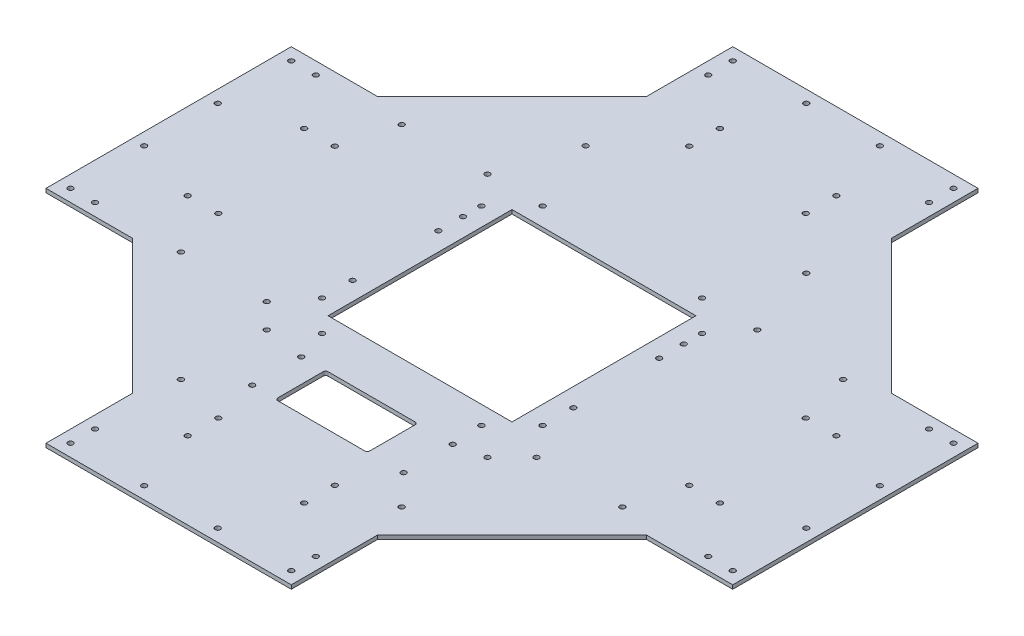
SolidWorks part; units mm, degrees
ref_plane "Front Plane" through (0, 0, 0) normal (0, 0, 1) x (1, 0, 0)
ref_plane "Top Plane" through (0, 0, 0) normal (0, 1, 0) x (1, 0, 0)
ref_plane "Right Plane" through (0, 0, 0) normal (1, 0, 0) x (0, 0, -1)
sketch "Sketch1" plane through (0, 0, 0) normal (0, 1, 0) x (1, 0, 0)
  line L0 (0, -280) -> (100, -280)
  line L1 (100, -280) -> (100, -209.6016)
  line L2 (280, -100) -> (209.6016, -100)
  line L3 (0, 0) -> (0, -280) construction
  line L4 (280, 0) -> (280, -100)
  line L5 (-280, 280) -> (280, 280) construction
  line L6 (-280, 280) -> (-280, -280) construction
  line L7 (-280, -280) -> (280, -280) construction
  line L8 (280, 280) -> (280, -280) construction
  line L9 (-280, 280) -> (280, -280) construction
  line L10 (-280, -280) -> (280, 280) construction
  line L11 (100, -209.6016) -> (209.6016, -100)
  line L12 (-280, 0) -> (-280, -100)
  line L13 (-280, -100) -> (-209.6016, -100)
  line L14 (-209.6016, -100) -> (-100, -209.6016)
  line L15 (-100, -280) -> (-100, -209.6016)
  line L16 (0, -280) -> (-100, -280)
  line L17 (0, 280) -> (-100, 280)
  line L18 (-100, 280) -> (-100, 209.6016)
  line L19 (-100, 209.6016) -> (-209.6016, 100)
  line L20 (-280, 100) -> (-209.6016, 100)
  line L21 (-280, 0) -> (-280, 100)
  line L22 (280, 0) -> (280, 100)
  line L23 (280, 100) -> (209.6016, 100)
  line L24 (209.6016, 100) -> (100, 209.6016)
  line L25 (100, 280) -> (100, 209.6016)
  line L26 (0, 280) -> (100, 280)
  line L27 (111.5258, -219.2889) -> (219.2889, -111.5258) construction
  line L28 (219.2889, -111.5258) -> (247.5732, -139.8101) construction
  line L29 (247.5732, -139.8101) -> (139.8101, -247.5732) construction
  line L30 (139.8101, -247.5732) -> (111.5258, -219.2889) construction
  line L31 (-100, -270) -> (100, -270) construction
  line L32 (-90, -280) -> (-90, 280) construction
  line L37 (-70, -70) -> (70, 70) construction
  line L38 (-70, 70) -> (70, -70) construction
  line L39 (-100, -260) -> (100, -260) construction
  line L40 (-280, 40) -> (280, 40) construction
  line L41 (0, 280) -> (0, 0) construction
  line L42 (-280, -90) -> (280, -90) construction
  line L43 (-260, -100) -> (-260, 100) construction
  line L44 (0, 0) -> (-280, 0) construction
  arc A0 (100, -280) -> (280, -100) centre (100, -100) ccw construction
  circle A1 centre (-47.5, -192) radius 2.125
  circle A2 centre (-47.5, -217) radius 2.125
  circle A3 centre (47.5, -217) radius 2.125
  circle A4 centre (47.5, -192) radius 2.125
  circle A5 centre (-192, 47.5) radius 2.125
  circle A6 centre (-217, 47.5) radius 2.125
  circle A7 centre (-192, -47.5) radius 2.125
  circle A8 centre (-217, -47.5) radius 2.125
  circle A9 centre (47.5, 192) radius 2.125
  circle A10 centre (47.5, 217) radius 2.125
  circle A11 centre (-47.5, 192) radius 2.125
  circle A12 centre (-47.5, 217) radius 2.125
  circle A13 centre (192, -47.5) radius 2.125
  circle A14 centre (217, -47.5) radius 2.125
  circle A15 centre (192, 47.5) radius 2.125
  circle A16 centre (217, 47.5) radius 2.125
  circle A17 centre (-90, -270) radius 2.125
  circle A18 centre (-30, -270) radius 2.125
  circle A19 centre (30, -270) radius 2.125
  circle A20 centre (90, -270) radius 2.125
  circle A21 centre (-270, 90) radius 2.125
  circle A22 centre (-270, 30) radius 2.125
  circle A23 centre (-270, -30) radius 2.125
  circle A24 centre (-270, -90) radius 2.125
  circle A25 centre (90, 270) radius 2.125
  circle A26 centre (30, 270) radius 2.125
  circle A27 centre (-30, 270) radius 2.125
  circle A28 centre (-90, 270) radius 2.125
  circle A29 centre (270, -90) radius 2.125
  circle A30 centre (270, -30) radius 2.125
  circle A31 centre (270, 30) radius 2.125
  circle A32 centre (270, 90) radius 2.125
  circle A33 centre (-90, -250) radius 2.125
  circle A34 centre (-90, -180) radius 2.125
  circle A35 centre (-90, -110) radius 2.125
  circle A36 centre (-90, -40) radius 2.125
  circle A37 centre (-90, 30) radius 2.125
  circle A38 centre (-90, 50) radius 2.125
  circle A39 centre (-90, 100) radius 2.125 construction
  circle A40 centre (-90, 150) radius 2.125
  circle A41 centre (-90, 200) radius 2.125 construction
  circle A42 centre (-90, 250) radius 2.125
  circle A43 centre (90, -250) radius 2.125
  circle A44 centre (90, -180) radius 2.125
  circle A45 centre (90, -110) radius 2.125
  circle A46 centre (90, -40) radius 2.125
  circle A47 centre (90, 30) radius 2.125
  circle A48 centre (90, 50) radius 2.125
  circle A49 centre (90, 100) radius 2.125 construction
  circle A50 centre (90, 150) radius 2.125
  circle A51 centre (90, 200) radius 2.125 construction
  circle A52 centre (90, 250) radius 2.125
  circle A53 centre (-250, -90) radius 2.125
  circle A54 centre (-180, -90) radius 2.125
  circle A55 centre (-110, -90) radius 2.125
  circle A56 centre (-110, 90) radius 2.125
  circle A57 centre (-180, 90) radius 2.125
  circle A58 centre (-250, 90) radius 2.125
  circle A59 centre (110, -90) radius 2.125
  circle A60 centre (180, -90) radius 2.125
  circle A61 centre (250, -90) radius 2.125
  circle A62 centre (110, 90) radius 2.125
  circle A63 centre (180, 90) radius 2.125
  circle A64 centre (250, 90) radius 2.125
  point P33 (0, 0)
  point P68 (0, 0)
  point P107 (0, 0)
  dimension "D10" = 25
  dimension "4.25" = 4.25
  dimension "D11" = 4.25
  dimension "D16" = 4.25
  dimension "D24" = 4.25
  dimension "D28" = 4.25
  dimension "D32" = 4.25
  dimension "D1" = 560
  dimension "D2" = 90
  dimension "D3" = 280
  dimension "D4" = 4
  dimension "D5" = 100
  dimension "D6" = 155
  dimension "D7" = 152.4
  dimension "D8" = 15
  dimension "D9" = 40
  dimension "D12" = 47.5
  dimension "D13" = 63
  dimension "D15" = 10
  dimension "D17" = 10
  dimension "D18" = 76.2
  dimension "D23" = 10
  dimension "D25" = 10
  dimension "D26" = 300
  dimension "D29" = 10
  dimension "D31" = 20
  dimension "D33" = 10
  dimension "D21" = 4
  dimension "D27" = 5
  dimension "D30" = 5
  dimension "D34" = 3
  dimension "D14" = 4
  dimension "D22" = 4
extrude "Boss-Extrude1" add sketch "Sketch1" along normal blind 3.175 contours L26 L17 L18 L19 L20 L21 L12 L13 L14 L15 L16 L0 L1 L11 L2 L4 L22 L23 L24 L25 region at (0, 0, -0.0137)
sketch "Sketch2" plane through (0, 3.175, 0) normal (0, 1, 0) x (1, 0, 0)
  line L0 (-90, -280) -> (-90, 280) construction
  line L1 (-75, -75) -> (75, -75)
  line L2 (-75, -75) -> (-75, 75)
  line L3 (-75, 75) -> (75, 75)
  line L4 (75, -75) -> (75, 75)
  line L5 (-75, -75) -> (75, 75) construction
  line L6 (-75, 75) -> (75, -75) construction
  line L7 (-90, -280) -> (-90, 280) construction
  line L8 (-75, 0) -> (75, 0) construction
  line L9 (0, 75) -> (0, -75) construction
  line L10 (-110, 90) -> (110, 90) construction
  line L11 (37.5, -135) -> (-37.5, -135) construction
  line L16 (-37.5, -155.5) -> (37.5, -155.5)
  line L17 (-37.5, -155.5) -> (-37.5, -114.5)
  line L18 (-37.5, -114.5) -> (37.5, -114.5)
  line L19 (37.5, -155.5) -> (37.5, -114.5)
  line L20 (-37.5, -155.5) -> (37.5, -114.5) construction
  line L21 (-37.5, -114.5) -> (37.5, -155.5) construction
  circle A0 centre (66.6, -115) radius 2.125
  circle A1 centre (-90, 65) radius 2.125
  circle A2 centre (-90, -65) radius 2.125
  circle A3 centre (90, -65) radius 2.125
  circle A4 centre (90, 65) radius 2.125
  circle A5 centre (-65, 90) radius 2.125
  circle A6 centre (65, 90) radius 2.125
  circle A7 centre (65, -90) radius 2.125
  circle A8 centre (-65, -90) radius 2.125
  circle A9 centre (66.6, -155) radius 2.125
  circle A10 centre (-56.9, -115) radius 2.1
  circle A11 centre (-56.9, -155) radius 2.1
  point P0 (0, 0)
  point P6 (0, -135)
  dimension "D3" = 4.25
  dimension "D5" = 4.25
  dimension "D11" = 4.25
  dimension "D14" = 4.2
  dimension "D1" = 150
  dimension "D2" = 150
  dimension "D4" = 10
  dimension "D6" = 10
  dimension "D7" = 75
  dimension "D8" = 41
  dimension "D9" = 0
  dimension "D10" = 135
  dimension "D12" = 20
  dimension "D13" = 66.6
  dimension "D15" = 19.4
  dimension "D16" = 20
extrude "Cut-Extrude1" cut sketch "Sketch2" against normal through all
fillet "Fillet1" radius 2 4 edges at (-37.5, 1.5875, 155.5) (37.5, 1.5875, 155.5) (37.5, 1.5875, 114.5) (-37.5, 1.5875, 114.5)
